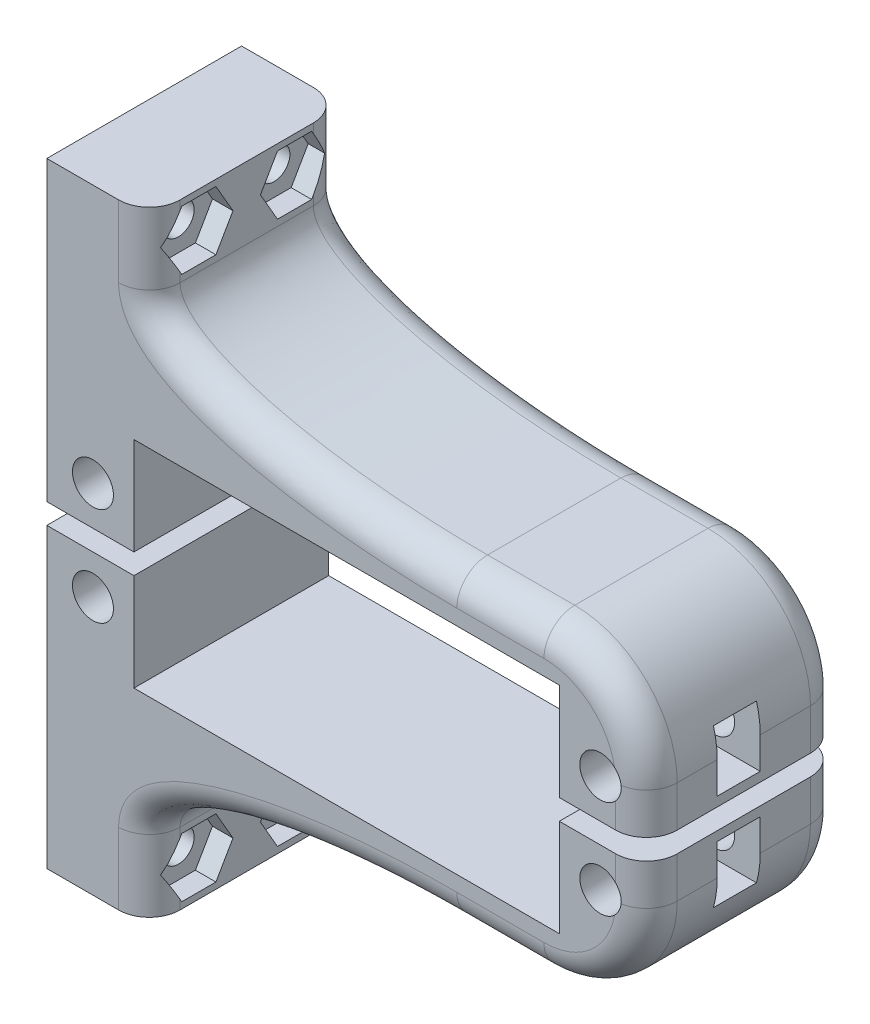
SolidWorks part; units mm, degrees
material "20% infill ABS"
ref_plane "Front" through (0, 0, 0) normal (0, 0, 1) x (1, 0, 0)
ref_plane "Top" through (0, 0, 0) normal (0, 1, 0) x (1, 0, 0)
ref_plane "Right" through (0, 0, 0) normal (1, 0, 0) x (0, 0, -1)
sketch "Sketch1" plane through (0, 0, 0) normal (0, 0, 1) x (1, 0, 0)
  line L0 (-0.5, -0.5) -> (41, -0.5)
  line L1 (-9, -5) -> (49.5, -5)
  line L3 (-9, 25) -> (49.5, 25)
  line L4 (0, 0) -> (40.5, 0)
  line L5 (40.5, 0) -> (40.5, 20)
  line L6 (40.5, 20) -> (0, 20)
  line L7 (0, 20) -> (0, 0)
  line L8 (0, 0) -> (40.5, 0) construction
  line L9 (40.5, 0) -> (40.5, 20) construction
  line L10 (40.5, 20) -> (0, 20) construction
  line L11 (0, 20) -> (0, 0) construction
  line L12 (49.5, -5) -> (49.5, 25)
  line L13 (47.5, 20) -> (47.5, 0) construction
  line L16 (41, -0.5) -> (41, 20.5)
  line L17 (-9, 25) -> (-9, -5)
  line L18 (41, 20.5) -> (-0.5, 20.5)
  line L19 (-0.5, 20.5) -> (-0.5, -0.5)
  dimension "D2" = 5
  dimension "D3" = 5
  dimension "D4" = 2
  dimension "D5" = 9
  dimension "D1" = 0
  dimension "D6" = 0.5
extrude "Boss-Extrude1" add sketch "Sketch1" against normal blind 19
ref_plane "Plane1" through (0, 0, -9) normal (0, 0, 1) x (1, 0, 0)
sketch "Sketch2" plane through (0, 0, -19) normal (0, 0, -1) x (-1, 0, 0)
  circle A0 centre (-45, 14.8) radius 2 construction
  circle A1 centre (-45, 5.2) radius 2 construction
  circle A2 centre (4.5, 14.8) radius 2 construction
  circle A3 centre (4.5, 5.2) radius 2 construction
  circle A4 centre (-45, 14.8) radius 2
  circle A5 centre (-45, 5.2) radius 2
  circle A6 centre (4.5, 14.8) radius 2
  circle A7 centre (4.5, 5.2) radius 2
extrude "Cut-Extrude1" cut sketch "Sketch2" against normal through all
sketch "Sketch3" plane through (0, 0, -9) normal (0, 0, 1) x (1, 0, 0)
  line L0 (49.5, 10) -> (-9, 10) construction
  line L7 (49.5, -5) -> (49.5, 25) construction
  line L8 (-9, 25) -> (-9, -5) construction
  line L9 (43.3349, 2.316) -> (41.6698, 5.2)
  line L10 (20.25, 20.5) -> (20.25, -0.5) construction
  line L13 (49.5, 17.684) -> (43.3349, 17.684)
  line L14 (41.6698, 5.2) -> (43.3349, 8.084)
  line L15 (43.3349, 17.684) -> (41.6698, 14.8)
  line L16 (41.6698, 14.8) -> (43.3349, 11.916)
  line L17 (43.3349, 11.916) -> (49.5, 11.916)
  line L30 (49.5, 17.684) -> (49.5, 11.916)
  line L33 (48.2283, 14.9763) -> (47.4201, 16.3763) [skipped]
  line L34 (46.7669, 12.0923) -> (47.5752, 13.4923) [skipped]
  line L35 (49.5, 17.684) -> (49.5, 11.916)
  line L36 (43.3349, 8.084) -> (49.5, 8.084)
  line L37 (49.5, 2.316) -> (49.5, 8.084)
  line L38 (49.5, 2.316) -> (43.3349, 2.316)
  line L39 (-1.1698, 14.8) -> (-2.8349, 11.916)
  line L40 (-2.8349, 17.684) -> (-1.1698, 14.8)
  line L41 (-9, 17.684) -> (-2.8349, 17.684)
  line L42 (-9, 17.684) -> (-9, 11.916)
  line L43 (-2.8349, 11.916) -> (-9, 11.916)
  line L44 (-2.8349, 8.084) -> (-9, 8.084)
  line L45 (-9, 2.316) -> (-9, 8.084)
  line L46 (-9, 2.316) -> (-2.8349, 2.316)
  line L47 (-2.8349, 2.316) -> (-1.1698, 5.2)
  line L48 (-1.1698, 5.2) -> (-2.8349, 8.084)
  line L49 (-0.5, -0.5) -> (41, -0.5) construction
  line L50 (41, 20.5) -> (-0.5, 20.5) construction
  circle A0 centre (45, 14.8) radius 2.8 construction
  point P1 (0, 0)
  point P2 (0, 0)
  point P3 (19.0027, -0.8607)
  point P21 (20.25, -0.5)
  point P37 (20.25, 20.5)
  dimension "D1" = 5.768
extrude "Cut-Extrude4" cut sketch "Sketch3" against normal mid plane 4.2 contours L43 L39 L40 L41 L42 | L47 L48 L44 L45 L46 | L38 L37 L36 L14 L9 | L30 L13 L15 L16 L17 | L41 L40 L39 L43 L42 region at (45.9847, 5.2, -9) region at (45.9847, 14.8, -9) region at (-5.4847, 14.8, -9) region at (-5.4847, 5.2, -9)
sketch "Sketch4" plane through (-9, 0, 0) normal (-1, 0, 0) x (0, 0, 1)
  line L0 (-19, 25) -> (-19, -5) construction
  line L1 (0, 25) -> (-19, 25)
  line L2 (0, 25) -> (0, 40)
  line L3 (0, 40) -> (-19, 40)
  line L4 (-19, 25) -> (-19, 40)
  dimension "D1" = 15
extrude "Boss-Extrude2" add sketch "Sketch4" against normal blind 10
fillet "Fillet1" radius 8 1 edges at (1, 25, -9.5) second distance 30 first distance on face at (1, 32.5, -9.5)
sketch "Sketch6" plane through (1, 0, 0) normal (1, 0, 0) x (0, 0, -1)
  line L0 (19, 36.5) -> (0, 36.5) construction
  line L1 (17.5, 36.5) -> (15.8349, 39.384)
  line L2 (15.8349, 39.384) -> (12.5048, 39.384)
  line L3 (12.5048, 39.384) -> (10.8397, 36.5)
  line L4 (10.8397, 36.5) -> (12.5048, 33.616)
  line L5 (12.5048, 33.616) -> (15.8349, 33.616)
  line L6 (15.8349, 33.616) -> (17.5, 36.5)
  line L7 (19, 40) -> (19, 33) construction
  line L8 (0, 33) -> (0, 40) construction
  line L9 (9.5, 40) -> (9.5, 33) construction
  line L10 (0, 40) -> (19, 40) construction
  line L11 (0, 33) -> (19, 33) construction
  line L12 (3.1651, 33.616) -> (1.5, 36.5)
  line L13 (6.4952, 33.616) -> (3.1651, 33.616)
  line L14 (8.1603, 36.5) -> (6.4952, 33.616)
  line L15 (6.4952, 39.384) -> (8.1603, 36.5)
  line L16 (3.1651, 39.384) -> (6.4952, 39.384)
  line L17 (1.5, 36.5) -> (3.1651, 39.384)
  circle A0 centre (14.1698, 36.5) radius 1.545
  circle A1 centre (14.1698, 36.5) radius 2.884 construction
  circle A2 centre (4.8302, 36.5) radius 1.545
  point P29 (0, 0)
  dimension "D2" = 3.09
  dimension "D1" = 5.768
  dimension "D3" = 1.5
extrude "Cut-Extrude5" cut sketch "Sketch6" against normal through all contours A0 | A2
extrude "Cut-Extrude6" cut sketch "Sketch6<4>" against normal blind 2
sketch "Sketch6<4>" plane through (1, 0, 0) normal (1, 0, 0) x (0, 0, -1) same geometry as "Sketch6"
ref_plane "Plane2" through (0, 10, 0) normal (0, 1, 0) x (1, 0, 0)
mirror "Mirror2" about plane through (0, 10, 0) normal (0, 1, 0) of "Cut-Extrude5", "Cut-Extrude6", "Boss-Extrude2"
fillet "Fillet2" radius 30 1 edges at (1, -5, -9.5) second distance 8 first distance on face at (25.25, -5, -9.5)
fillet "Fillet3" radius 10 2 edges at (49.5, -5, -9.5) (49.5, 25, -9.5)
fillet "Fillet4" radius 3 9 edges at (46.5711, 22.0711, -19) (49.5, 10, -19) (46.5711, -2.0711, -19)
fillet "Fillet5" radius 3 9 edges at (46.5711, 22.0711, 0) (46.5711, -2.0711, 0) (49.5, 10, 0)
sketch "Sketch7" plane through (0, 0, 0) normal (0, 0, 1) x (1, 0, 0)
  line L1 (53.9196, 11) -> (-14.7387, 11)
  line L2 (53.9196, 11) -> (53.9196, 9)
  line L3 (53.9196, 9) -> (-14.7387, 9)
  line L4 (-14.7387, 11) -> (-14.7387, 9)
  line L5 (10.494, 10) -> (-10.494, 10) construction
  point P4 (53.9196, 10)
  dimension "D1" = 2
extrude "Cut-Extrude7" cut sketch "Sketch7" against normal through all
